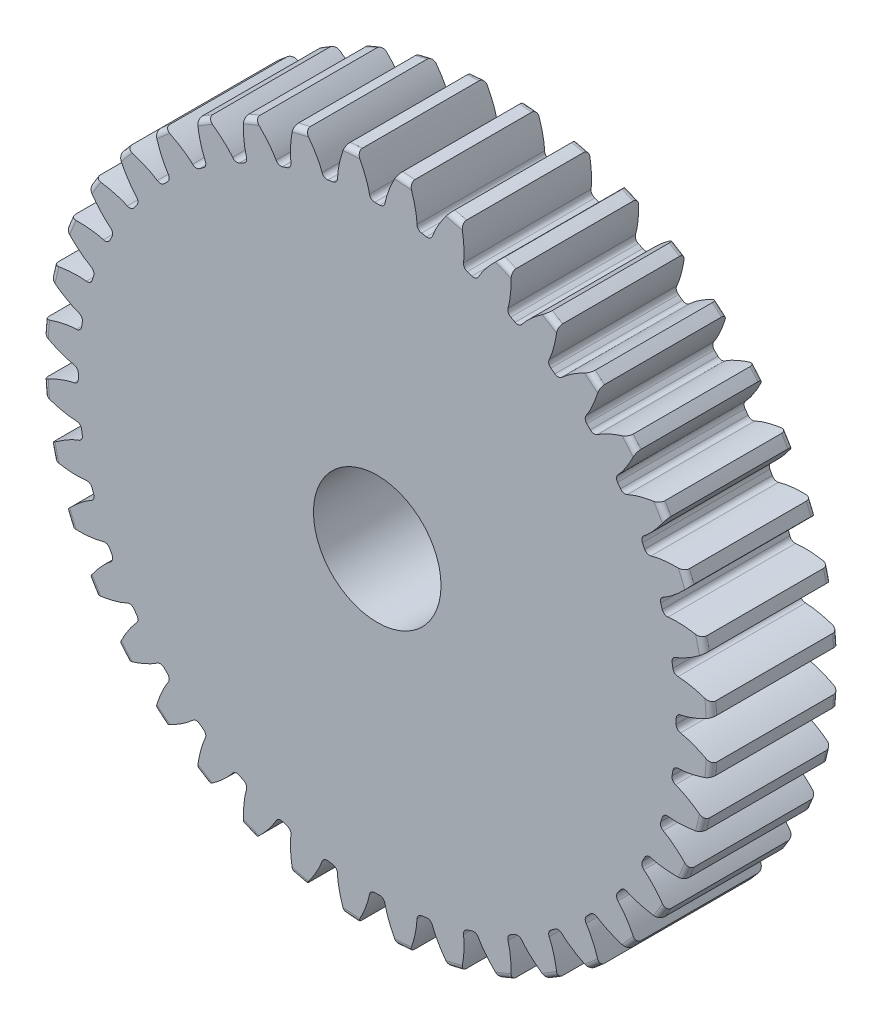
SolidWorks part; units mm, degrees
ref_plane "Front Plane" through (0, 0, 0) normal (0, 0, 1) x (1, 0, 0)
ref_plane "Top Plane" through (0, 0, 0) normal (0, 1, 0) x (1, 0, 0)
ref_plane "Right Plane" through (0, 0, 0) normal (1, 0, 0) x (0, 0, -1)
sketch "Sketch1" plane through (0, 0, 0) normal (0, 0, 1) x (1, 0, 0)
  line L0 (0, 0) -> (0, 15.875) construction
  line L1 (-5.1021, 17.732) -> (5.1021, 14.018) construction
  circle A0 centre (0, 0) radius 14.8828 construction
  circle A1 centre (0, 0) radius 16.6687 construction
  circle A2 centre (0, 0) radius 15.875 construction
  circle A3 centre (0, 0) radius 14.9176 construction
  circle A4 centre (0, 0) radius 3.175 construction
  circle A5 centre (0, 0) radius 9.144 construction
  point P8 (406.4, 0)
  point P13 (508, 0)
  dimension "OD | Outside Diameter" = 33.3375
  dimension "Root Diameter" = 29.7656
  dimension "Gear Pitch Diameter" = 31.75
  dimension "Base Diameter" = 29.8352
  dimension "For Shaft Diameter" = 6.35
  dimension "Hub Diameter" = 18.288
  dimension "Pressure Angle" = 20
  dimension "Number of Teeth" = 1016
  dimension "Gear Pitch | Diametral Pitch" = 812.8
sketch "Sketch2" plane through (0, 0, 0) normal (1, 0, 0) x (0, 0, -1)
  line L0 (-7.1374, 0) -> (7.1374, 0) construction
  line L1 (-6.35, 16.6687) -> (6.35, 16.6687) construction
  line L2 (0, 55) -> (0, -55) construction
  point P2 (0, 16.6687)
  point P4 (0.7874, 0)
  point P6 (0.7874, 16.6687)
  dimension "D1" = 6.35
  dimension "D2" = 6.35
sketch "Sketch3" plane through (0, 0, 0) normal (0, 0, 1) x (1, 0, 0)
  circle A0 centre (0, 0) radius 16.6687
  circle A1 centre (0, 0) radius 16.6687 construction
extrude "Boss-Extrude1" add sketch "Sketch3" against normal up to vertex (7.1374 mm away) and the other way up to vertex (7.1374 mm away) up to point (0, 0, -7.1374) other way up to point (0, 0, 7.1374)
sketch "Sketch5" plane through (0, 0, 0) normal (1, 0, 0) x (0, 0, -1)
  line L1 (-7.1374, 16.6687) -> (0.7874, 16.6687)
  line L2 (-7.1374, 16.6687) -> (-7.1374, 9.144)
  line L3 (-7.1374, 9.144) -> (0.7874, 9.144)
  line L4 (0.7874, 16.6687) -> (0.7874, 9.144)
  line L11 (7.1374, 3.175) -> (-7.1374, 3.175)
  line L12 (7.1374, 3.175) -> (7.1374, 0)
  line L13 (7.1374, 0) -> (-7.1374, 0)
  line L14 (-7.1374, 3.175) -> (-7.1374, 0)
  point P5 (0, 3.175)
  point P12 (0, 9.144)
revolve "Cut-Revolve1" cut sketch "Sketch5" angle 360 about L0
fillet "Fillet2" radius 0.2663 6 edges at (16.6687, 0, -7.1374) (3.175, 0, -7.1374) (3.175, 0, 7.1374) (9.144, 0, -0.7874) (16.6687, 0, -0.7874) (9.144, 0, 7.1374)
sketch "Sketch4" plane through (0, 0, 0) normal (0, 0, 1) x (1, 0, 0)
  line L0 (0, 0) -> (14.8784, 0.3626) construction
  line L2 (0, 0) -> (14.8784, -0.3626) construction
  line L4 (14.8784, 0.3626) -> (14.9132, 0.3634)
  line L5 (14.9132, -0.3634) -> (14.8784, -0.3626)
  arc A0 (14.8784, 0.3626) -> (14.8784, -0.3626) centre (0, 0) cw
  arc A3 (16.6383, 1.0067) -> (16.6383, -1.0067) centre (0, 0) cw
  circle A4 centre (0, 0) radius 16.6687 construction
  spline S0 degree 4 poles (14.9132, 0.3634) (14.9159, 0.3635) (14.9236, 0.3639) (14.9381, 0.3649) (14.9618, 0.3671) (14.9919, 0.3706) (15.0308, 0.376) (15.0766, 0.3835) (15.1268, 0.3928) (15.1814, 0.4042) (15.2358, 0.4166) (15.29, 0.4301) (15.3439, 0.4444) (15.4091, 0.4628) (15.4872, 0.4863) (15.5783, 0.516) (15.6814, 0.5524) (15.7862, 0.5921) (15.8891, 0.6335) (15.9927, 0.678) (16.0929, 0.7228) (16.1965, 0.7721) (16.2921, 0.8189) (16.3988, 0.8743) (16.4848, 0.9199) (16.5978, 0.9832) (16.6645, 1.0215) (16.7423, 1.0675) (16.7768, 1.0885) (16.798, 1.1014) knots 0 0 0 0 0 0.005377 0.015084 0.028532 0.04661 0.064855 0.092111 0.119476 0.146842 0.174209 0.201575 0.228941 0.256307 0.307035 0.361767 0.4165 0.471232 0.525964 0.580697 0.635429 0.690161 0.744894 0.799626 0.854358 0.909091 0.954545 1 1 1 1 1 construction
  spline S1 degree 4 poles (14.9132, 0.3634) (14.9159, 0.3635) (14.9236, 0.3639) (14.9381, 0.3649) (14.9618, 0.3671) (14.9919, 0.3706) (15.0308, 0.376) (15.0766, 0.3835) (15.1268, 0.3928) (15.1814, 0.4042) (15.2358, 0.4166) (15.29, 0.4301) (15.3439, 0.4444) (15.4091, 0.4628) (15.4872, 0.4863) (15.5783, 0.516) (15.6814, 0.5524) (15.7862, 0.5921) (15.8891, 0.6335) (15.9927, 0.678) (16.0929, 0.7228) (16.1965, 0.7721) (16.2921, 0.8189) (16.3988, 0.8743) (16.4848, 0.9199) (16.5733, 0.9695) (16.6163, 0.994) (16.6383, 1.0067) knots 0 0 0 0 0 0.005377 0.015084 0.028532 0.04661 0.064855 0.092111 0.119476 0.146842 0.174209 0.201575 0.228941 0.256307 0.307035 0.361767 0.4165 0.471232 0.525964 0.580697 0.635429 0.690161 0.744894 0.799626 0.854358 0.909091 0.909091 0.909091 0.909091 0.909091
  spline S2 degree 4 poles (14.9132, -0.3634) (14.9159, -0.3635) (14.9236, -0.3639) (14.9381, -0.3649) (14.9618, -0.3671) (14.9919, -0.3706) (15.0308, -0.376) (15.0766, -0.3835) (15.1268, -0.3928) (15.1814, -0.4042) (15.2358, -0.4166) (15.29, -0.4301) (15.3439, -0.4444) (15.4091, -0.4628) (15.4872, -0.4863) (15.5783, -0.516) (15.6814, -0.5524) (15.7862, -0.5921) (15.8891, -0.6335) (15.9927, -0.678) (16.0929, -0.7228) (16.1965, -0.7721) (16.2921, -0.8189) (16.3988, -0.8743) (16.4848, -0.9199) (16.5978, -0.9832) (16.6645, -1.0215) (16.7423, -1.0675) (16.7768, -1.0885) (16.798, -1.1014) knots 0 0 0 0 0 0.005377 0.015084 0.028532 0.04661 0.064855 0.092111 0.119476 0.146842 0.174209 0.201575 0.228941 0.256307 0.307035 0.361767 0.4165 0.471232 0.525964 0.580697 0.635429 0.690161 0.744894 0.799626 0.854358 0.909091 0.954545 1 1 1 1 1 construction
  spline S3 degree 4 poles (14.9132, -0.3634) (14.9159, -0.3635) (14.9236, -0.3639) (14.9381, -0.3649) (14.9618, -0.3671) (14.9919, -0.3706) (15.0308, -0.376) (15.0766, -0.3835) (15.1268, -0.3928) (15.1814, -0.4042) (15.2358, -0.4166) (15.29, -0.4301) (15.3439, -0.4444) (15.4091, -0.4628) (15.4872, -0.4863) (15.5783, -0.516) (15.6814, -0.5524) (15.7862, -0.5921) (15.8891, -0.6335) (15.9927, -0.678) (16.0929, -0.7228) (16.1965, -0.7721) (16.2921, -0.8189) (16.3988, -0.8743) (16.4848, -0.9199) (16.5733, -0.9695) (16.6163, -0.994) (16.6383, -1.0067) knots 0 0 0 0 0 0.005377 0.015084 0.028532 0.04661 0.064855 0.092111 0.119476 0.146842 0.174209 0.201575 0.228941 0.256307 0.307035 0.361767 0.4165 0.471232 0.525964 0.580697 0.635429 0.690161 0.744894 0.799626 0.854358 0.909091 0.909091 0.909091 0.909091 0.909091
  dimension "D1" = 29.7656
extrude "Cut-Extrude1" cut sketch "Sketch4" against normal through all both and the other way through all
fillet "Fillet1" radius 0.2663 2 edges at (14.8784, -0.3626, -3.9624) (14.8784, 0.3626, -3.9624)
pattern_circular "CirPattern1" count 40 over 360 about axis through (0, 0, 7.1374) along (0, 0, -1) of "Cut-Extrude1", "Fillet1"
sketch "Sketch6" plane through (0, 0, 0) normal (0, 1, 0) x (1, 0, 0)
  line L0 (-12.1935, 0.7874) -> (-10.9517, 0.7874) construction
  line L1 (-11.5726, 0.7874) -> (13.0937, 0.7874)
  line L2 (-11.5726, 0.7874) -> (-11.5726, -9.5826)
  line L3 (-11.5726, -9.5826) -> (13.0937, -9.5826)
  line L4 (13.0937, 0.7874) -> (13.0937, -9.5826)
extrude "Cut-Extrude2" cut sketch "Sketch6" against normal through all both and the other way through all
equation "\"Root Diameter@Sketch1\"=\"Root Diameter\""
equation "\"OD | Outside Diameter@Sketch1\"=\"Outside Diameter\""
equation "\"D1@CirPattern1\"=\"Number of Teeth\""
equation "\"Diametral Pitch\"=32"
equation "\"Number of Teeth\"= 40"
equation "\"Pressure Angle\"=20"
equation "\"Pitch Diameter\"= \"Number of Teeth\" / \"Diametral Pitch\""
equation "\"Base Diameter\"= \"Pitch Diameter\" * cos ( \"Pressure Angle\" )"
equation "\"Outside Diameter\"= ( \"Number of Teeth\" + 2 ) / \"Diametral Pitch\""
equation "\"Dedendum\"= 1.25 / \"Diametral Pitch\""
equation "\"Root Diameter\"= \"Pitch Diameter\" - ( 2 * \"Dedendum\" )"
equation "\"Pitch Angle\"= 360deg / \"Number of Teeth\""
equation "\"Alpha\"= sqr ( \"Pitch Diameter\" ^ 2 - \"Base Diameter\" ^ 2 ) / \"Base Diameter\" * 180 / PI - \"Pressure Angle\""
equation "\"Beta\"= ( \"Pitch Angle\" / 4 - \"Alpha\" )"
equation "\"Phi\"= sqr ( ( \"Outside Diameter\" / 2 ) ^ 2 - ( \"Base Diameter\" / 2 ) ^ 2 ) / ( \"Base Diameter\" / 2 )"
equation "\"Addendum\"= 1 / \"Diametral Pitch\""
equation "\"WorkingDepth\"= 2 / \"Diametral Pitch\""
equation "\"WholeDepth\"= 2.25 / \"Diametral Pitch\""
equation "\"Clearance\"= 0.25 / \"Diametral Pitch\""
equation "\"ToothThickness\"= ( pi * 2 ) / \"Diametral Pitch\""
equation "\"CircularPitch\"= pi / \"Diametral Pitch\""
equation "\"Number of Teeth@Sketch1\"=\"Number of Teeth\""
equation "\"Gear Pitch | Diametral Pitch@Sketch1\"=\"Diametral Pitch\""
equation "\"Pressure Angle@Sketch1\"=\"Pressure Angle\""
equation "\"Gear Pitch Diameter@Sketch1\"=\"Pitch Diameter\""
equation "\"Base Diameter@Sketch1\"=\"Base Diameter\""
equation "\"Fillet\"= \"Clearance\" * cos ( \"Pressure Angle\" ) * tan ( ( 90 + \"Pressure Angle\" ) / 2 )"
equation "\"D1@Fillet1\"=\"Fillet\""
equation "\"D1@Sketch4\"=if( \"Base Diameter\">\"Root Diameter\",\"Root Diameter\",\"Base Diameter\"-.00001)"
equation "\"D1@Fillet2\"=\"Fillet\""
